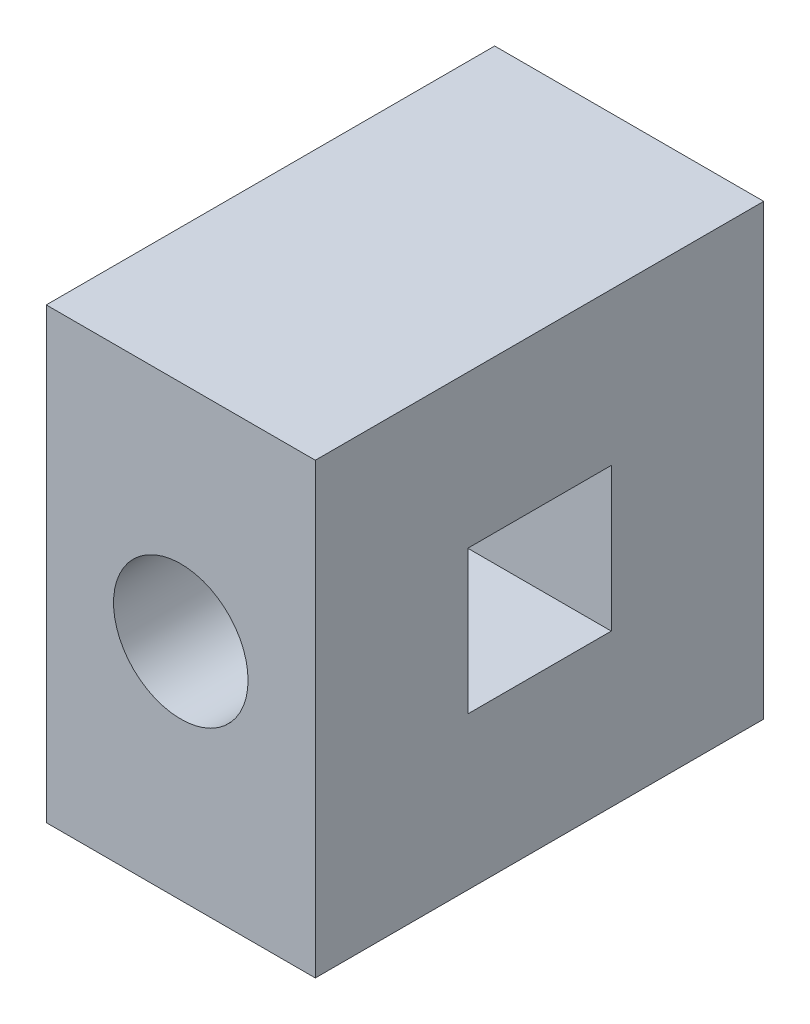
SolidWorks part; units mm, degrees
ref_plane "Front Plane" through (0, 0, 0) normal (0, 0, 1) x (1, 0, 0)
ref_plane "Top Plane" through (0, 0, 0) normal (0, 1, 0) x (1, 0, 0)
ref_plane "Right Plane" through (0, 0, 0) normal (1, 0, 0) x (0, 0, -1)
sketch "Sketch1" plane through (0, 0, 0) normal (0, 0, 1) x (1, 0, 0)
  line L0 (0, 10) -> (6, 0) construction
  line L1 (0, 0) -> (6, 0)
  line L2 (0, 0) -> (0, 10)
  line L3 (0, 10) -> (6, 10)
  line L4 (6, 0) -> (6, 10)
  circle A0 centre (3, 5) radius 1.5
  dimension "D3" = 3
  dimension "D1" = 6
  dimension "D2" = 10
extrude "Boss-Extrude1" add sketch "Sketch1" along normal blind 10
sketch "Sketch2" plane through (6, 0, 0) normal (1, 0, 0) x (0, 0, -1)
  line L0 (-10, 10) -> (0, 0) construction
  line L2 (-6.6, 3.4) -> (-3.4, 3.4)
  line L3 (-6.6, 3.4) -> (-6.6, 6.6)
  line L4 (-6.6, 6.6) -> (-3.4, 6.6)
  line L5 (-3.4, 3.4) -> (-3.4, 6.6)
  line L6 (-6.6, 3.4) -> (-3.4, 6.6) construction
  line L7 (-6.6, 6.6) -> (-3.4, 3.4) construction
  point P4 (-5, 5)
  dimension "D1" = 3.2
extrude "Cut-Extrude1" cut sketch "Sketch2" against normal through all
extrude "Boss-Extrude2" add sketch "Sketch1<3>" along normal up to surface (3.4 mm away) contours L0 L2 L1 A0 | L3 L0 A0 L4 | A0 region at (4.0606, 6.8455, 0) region at (1.9394, 3.1545, 0) up to face at (1.5, 5, 3.4)
sketch "Sketch1<3>" plane through (0, 0, 0) normal (0, 0, 1) x (1, 0, 0) same geometry as "Sketch1"
